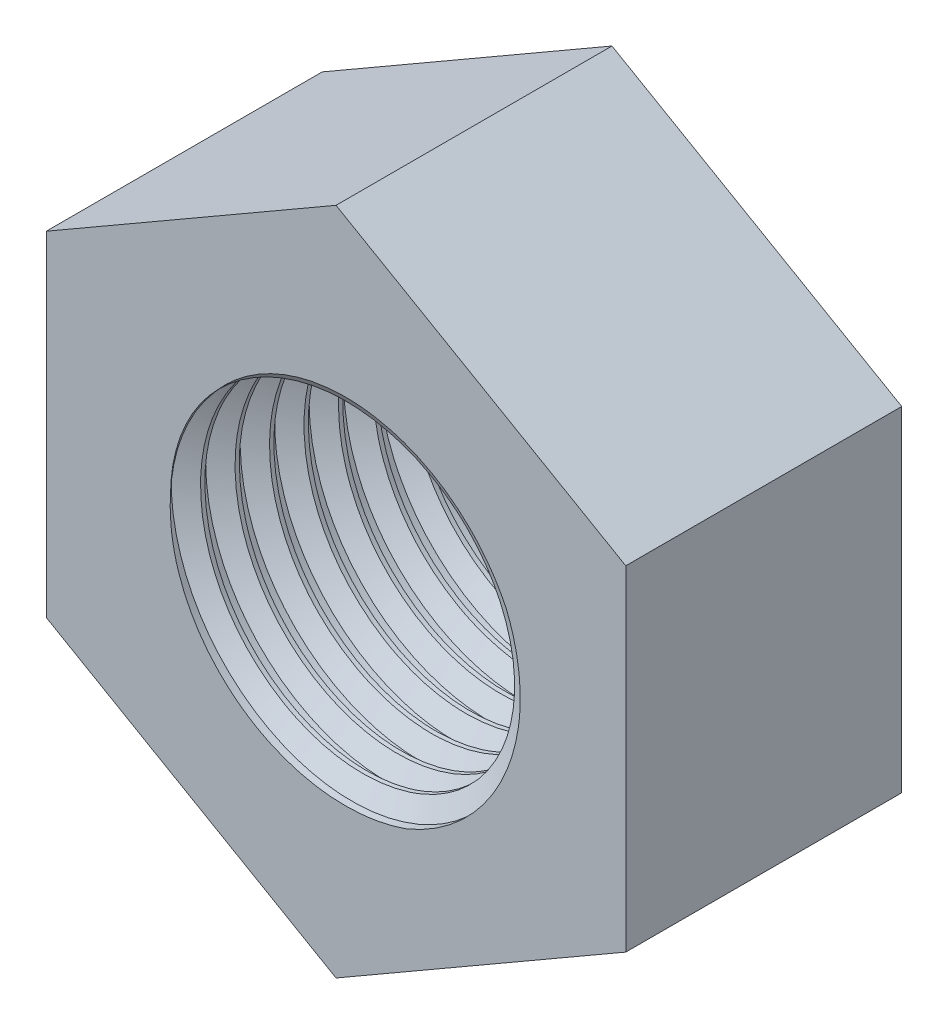
SolidWorks part; units mm, degrees
material "Cobalt"
ref_plane "Front Plane" through (0, 0, 0) normal (0, 0, 1) x (1, 0, 0)
ref_plane "Top Plane" through (0, 0, 0) normal (0, 1, 0) x (1, 0, 0)
ref_plane "Right Plane" through (0, 0, 0) normal (1, 0, 0) x (0, 0, -1)
sketch "Sketch1" plane through (0, 0, 0) normal (0, 0, 1) x (1, 0, 0)
  line L1 (0, -12.1244) -> (10.5, -6.0622)
  line L2 (10.5, -6.0622) -> (10.5, 6.0622)
  line L3 (10.5, 6.0622) -> (0, 12.1244)
  line L4 (0, 12.1244) -> (-10.5, 6.0622)
  line L5 (-10.5, 6.0622) -> (-10.5, -6.0622)
  line L6 (-10.5, -6.0622) -> (0, -12.1244)
  circle A0 centre (0, 0) radius 10.5 construction
  circle A1 centre (0, 0) radius 6
  dimension "D2" = 12
  dimension "D1" = 21
extrude "Boss-Extrude1" add sketch "Sketch1" along normal blind 10
thread "Thread1" pitch 1.25 method cut profile "Thread Profile1" start angle 0, offset 5, length 35, pitch 1.25, diameter 12
ref_plane "Plane1" through (-6, 0, 15) normal (0, 1, 0) x (1, 0, 0)
sketch "Thread Profile1" plane through (-6, 0, 15) normal (0, 1, 0) x (1, 0, 0)
  line L0 (0, 0) -> (0, 1.25) construction
  line L11 (0, 0) -> (0, 1.0937)
  line L12 (0, 1.0937) -> (-0.6766, 0.7031)
  line L13 (-0.6766, 0.7031) -> (-0.6766, 0.3906)
  line L15 (-0.6766, 0.3906) -> (0, 0)
  line L17 (-0.6766, 0.5469) -> (0, 0.5469) construction
  point P2 (0, 0)
  dimension "Pitch" = 1.25
  dimension "Profile_Angle" = 60
  dimension "Profile_Land" = 0.3125
  dimension "Profile_Height" = 0.6766
